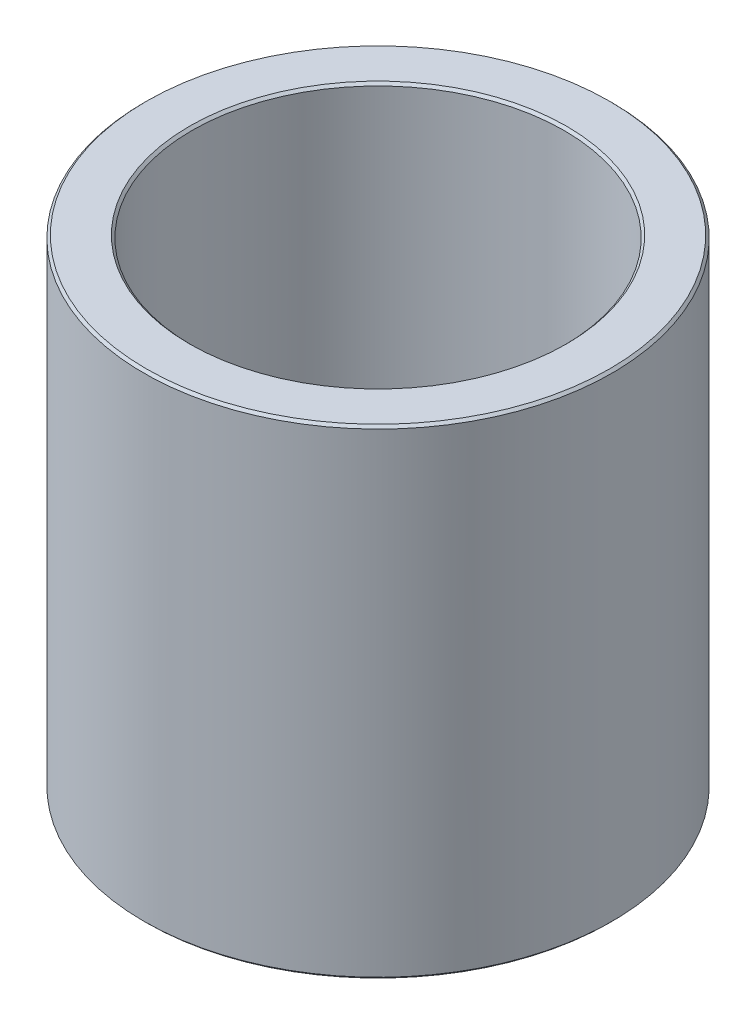
SolidWorks part; units mm, degrees
ref_plane "Front Plane" through (0, 0, 0) normal (0, 0, 1) x (1, 0, 0)
ref_plane "Top Plane" through (0, 0, 0) normal (0, 1, 0) x (1, 0, 0)
ref_plane "Right Plane" through (0, 0, 0) normal (1, 0, 0) x (0, 0, -1)
sketch "Sketch1" plane through (0, 0, 0) normal (0, 1, 0) x (1, 0, 0)
  circle A0 centre (0, 0) radius 52.5
  dimension "SLEEVE_OD" = 105
extrude "Boss-Extrude1" add sketch "Sketch1" along normal blind 107.5352
sketch "Sketch2" plane through (0, 0, 0) normal (0, 1, 0) x (1, 0, 0)
  circle A0 centre (0, 0) radius 41.7221
  dimension "BORE_D" = 83.4442
extrude "Cut-Extrude1" cut sketch "Sketch2" along normal through all
chamfer "Chamfer1" distance 0.553 angle 45 4 edges at (0, 107.5352, 41.7221) (0, 0, 41.7221) (0, 0, 52.5) (0, 107.5352, 52.5)
